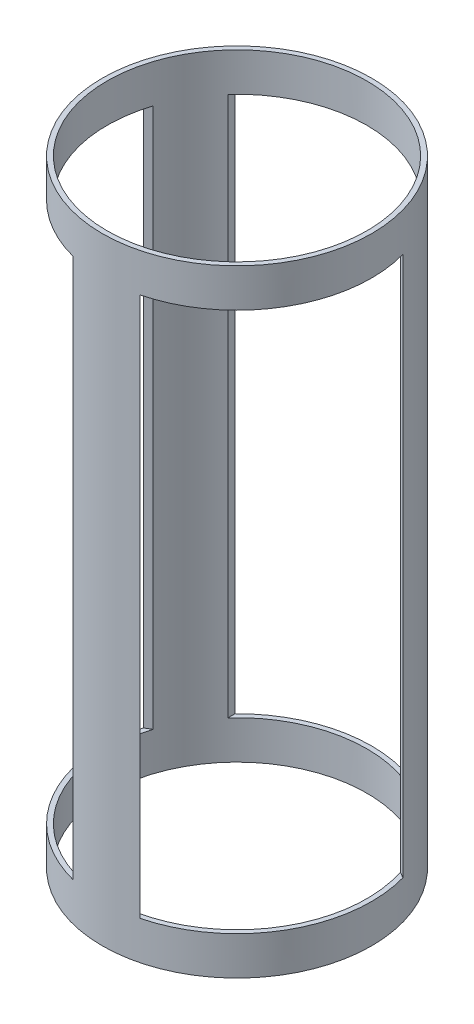
SolidWorks part; units mm, degrees
material "6061-T6 (SS)"
ref_plane "Front Plane" through (0, 0, 0) normal (0, 0, 1) x (1, 0, 0)
ref_plane "Top Plane" through (0, 0, 0) normal (0, 1, 0) x (1, 0, 0)
ref_plane "Right Plane" through (0, 0, 0) normal (1, 0, 0) x (0, 0, -1)
sketch "Sketch1" plane through (0, 0, 0) normal (0, 1, 0) x (1, 0, 0)
  circle A0 centre (0, 0) radius 88.9
  circle A1 centre (0, 0) radius 85.725
  dimension "D1" = 177.8
  dimension "D2" = 171.45
extrude "Boss-Extrude1" add sketch "Sketch1" along normal mid plane 407.162
sketch "Sketch2" plane through (0, 0, 0) normal (0, 0, 1) x (1, 0, 0)
  line L0 (85.725, 203.581) -> (-85.725, 203.581) construction
  line L1 (-63.5, -178.181) -> (63.5, -178.181)
  line L2 (-63.5, -178.181) -> (-63.5, 178.181)
  line L3 (-63.5, 178.181) -> (63.5, 178.181)
  line L4 (63.5, -178.181) -> (63.5, 178.181)
  line L5 (-63.5, -178.181) -> (63.5, 178.181) construction
  line L6 (-63.5, 178.181) -> (63.5, -178.181) construction
  line L7 (88.9, -203.581) -> (88.9, 203.581) construction
  point P0 (0, 0)
  dimension "D1" = 25.4
  dimension "D2" = 25.4
extrude "Cut-Extrude1" cut sketch "Sketch2" against normal up to surface (62.217 mm away) up to face at (0, 203.581, 88.9)
pattern_circular "CirPattern1" count 3 over 360 about axis through (0, 203.581, 0) along (0, -1, 0) of "Cut-Extrude1"
ref_plane "Plane1" through (88.9, 0, 0) normal (1, 0, 0) x (0, 0, -1)
sketch "Sketch4" plane through (88.9, 0, 0) normal (1, 0, 0) x (0, 0, -1)
  line L0 (0, 97.79) -> (0, -97.79) construction
  line L1 (88.9, 203.581) -> (-88.9, 203.581) construction
  circle A0 centre (0, 197.231) radius 1.4351
  dimension "D1" = 2.8702
  dimension "D2" = 6.35
extrude "Cut-Extrude3" [suppressed] cut sketch "Sketch4" against normal blind 15.24
pattern_circular "CirPattern3" [suppressed] count 12 over 360 of bodies 107
mirror "Mirror1" [suppressed] about plane through (0, 0, 0) normal (0, 1, 0)
ref_plane "Plane2" through (0, 0, 88.9) normal (0, 0, 1) x (1, 0, 0)
sketch "Sketch5" [suppressed] plane through (0, 0, 88.9) normal (0, 0, 1) x (1, 0, 0)
  circle A0 centre (0, -65.7606) radius 1.4351
  circle A1 centre (0, 65.7606) radius 1.4351
  circle A2 centre (0, 197.231) radius 1.4351 construction
  circle A3 centre (0, -197.231) radius 1.4351 construction
  dimension "D1" = 131.4704
  dimension "D2" = 131.4704
  dimension "D3" = 2.8702
  dimension "D4" = 2.8702
extrude "Cut-Extrude4" [suppressed] cut sketch "Sketch5" against normal blind 46.482
pattern_circular "CirPattern4" [suppressed] count 3 over 360 of bodies 110
